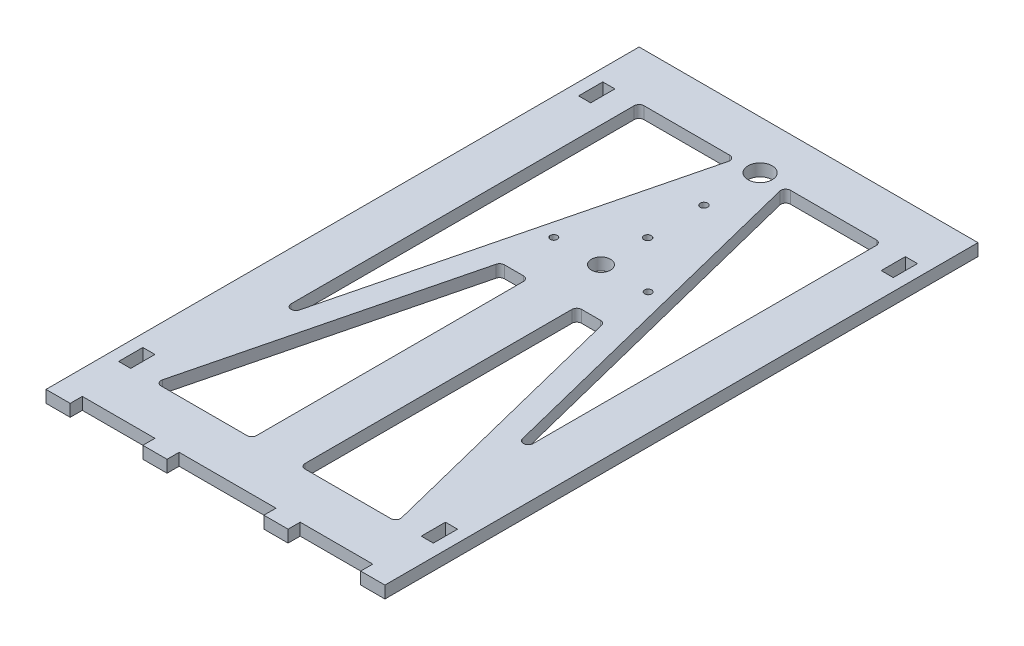
SolidWorks part; units mm, degrees
material "Beech"
ref_plane "Front Plane" through (0, 0, 0) normal (0, 0, 1) x (1, 0, 0)
ref_plane "Top Plane" through (0, 0, 0) normal (0, 1, 0) x (1, 0, 0)
ref_plane "Right Plane" through (0, 0, 0) normal (1, 0, 0) x (0, 0, -1)
sketch "Sketch1" plane through (0, 0, 0) normal (0, 1, 0) x (1, 0, 0)
  line L0 (0, 0) -> (177.8, 0)
  line L1 (0, 0) -> (0, 304.8)
  line L2 (177.8, 0) -> (177.8, 304.8)
  line L3 (0, 304.8) -> (177.8, 304.8)
  line L4 (0, 0) -> (12.7, 0)
  line L5 (0, 0) -> (0, -6.35)
  line L6 (12.7, 0) -> (12.7, -6.35)
  line L7 (0, -6.35) -> (12.7, -6.35)
  line L8 (177.8, 0) -> (165.1, 0)
  line L9 (177.8, 0) -> (177.8, -6.35)
  line L10 (165.1, 0) -> (165.1, -6.35)
  line L11 (177.8, -6.35) -> (165.1, -6.35)
  line L12 (127, 0) -> (114.3, 0)
  line L13 (127, 0) -> (127, -6.35)
  line L14 (114.3, 0) -> (114.3, -6.35)
  line L15 (127, -6.35) -> (114.3, -6.35)
  line L16 (50.8, 0) -> (63.5, 0)
  line L17 (50.8, 0) -> (50.8, -6.35)
  line L18 (63.5, 0) -> (63.5, -6.35)
  line L19 (50.8, -6.35) -> (63.5, -6.35)
  line L20 (165.1, 279.4) -> (171.45, 279.4)
  line L21 (165.1, 279.4) -> (165.1, 266.7)
  line L22 (171.45, 279.4) -> (171.45, 266.7)
  line L23 (165.1, 266.7) -> (171.45, 266.7)
  line L24 (6.35, 279.4) -> (12.7, 279.4)
  line L25 (6.35, 279.4) -> (6.35, 266.7)
  line L26 (12.7, 279.4) -> (12.7, 266.7)
  line L27 (6.35, 266.7) -> (12.7, 266.7)
  line L28 (6.35, 38.1) -> (12.7, 38.1)
  line L29 (6.35, 38.1) -> (6.35, 25.4)
  line L30 (12.7, 38.1) -> (12.7, 25.4)
  line L31 (6.35, 25.4) -> (12.7, 25.4)
  line L32 (165.1, 38.1) -> (171.45, 38.1)
  line L33 (165.1, 38.1) -> (165.1, 25.4)
  line L34 (171.45, 38.1) -> (171.45, 25.4)
  line L35 (165.1, 25.4) -> (171.45, 25.4)
  line L36 (76.2, 279.4) -> (25.4, 279.4)
  line L37 (25.4, 279.4) -> (25.4, 76.2)
  line L38 (25.4, 76.2) -> (76.2, 279.4)
  line L39 (101.6, 279.4) -> (152.4, 279.4)
  line L40 (152.4, 279.4) -> (152.4, 76.2)
  line L41 (152.4, 76.2) -> (101.6, 279.4)
  line L42 (25.4, 25.4) -> (61.675, 170.5)
  line L43 (61.675, 170.5) -> (76.2, 170.5)
  line L44 (76.2, 170.5) -> (76.2, 25.4)
  line L45 (76.2, 25.4) -> (25.4, 25.4)
  line L46 (101.6, 170.5) -> (116.125, 170.5)
  line L47 (116.125, 170.5) -> (152.4, 25.4)
  line L48 (152.4, 25.4) -> (101.6, 25.4)
  line L49 (101.6, 25.4) -> (101.6, 170.5)
  circle A0 centre (88.9, 279.4) radius 6.35
  circle A1 centre (88.9, 249.9) radius 1.935
  circle A2 centre (88.9, 220.4) radius 1.935
  circle A3 centre (88.9, 195.9) radius 5
  circle A4 centre (113.65, 195.9) radius 1.8542
  circle A5 centre (64.15, 195.9) radius 1.8542
  point P21 (88.9, 304.8)
  dimension "D8" = 12.7
  dimension "D14" = 3.87
  dimension "D15" = 3.87
  dimension "D18" = 10
  dimension "D19" = 3.7084
  dimension "D1" = 177.8
  dimension "D2" = 6.35
  dimension "D3" = 12.7
  dimension "D4" = 50.8
  dimension "D5" = 50.8
  dimension "D6" = 304.8
  dimension "D7" = 25.4
  dimension "D9" = 25.4
  dimension "D10" = 25.4
  dimension "D11" = 50.8
  dimension "D12" = 12.7
  dimension "D13" = 12.7
  dimension "D16" = 29.5
  dimension "D17" = 29.5
  dimension "D20" = 24.75
  dimension "D21" = 24.75
  dimension "D22" = 24.5
  dimension "D23" = 203.2
  dimension "D24" = 25.4
extrude "Front Panel" add sketch "Sketch1" along normal blind 6.35 contours L3 L1 L0 L2 A0 L35 L33 L32 L34 L31 L29 L28 L30 L27 L25 L24 L26 L23 L21 L20 L22 | L5 L7 L6 L0 | L17 L19 L18 L0 | L15 L13 L0 L14 | L11 L9 L0 L10 region at (88.9, 0, -152.6728) region at (6.35, 0, 3.175) region at (57.15, 0, 3.175) region at (171.45, 0, 3.175) region at (120.65, 0, 3.175)
fillet "Fillet1" radius 2.54 14 edges at (152.4, 3.175, -76.2) (152.4, 3.175, -279.4) (101.6, 3.175, -279.4) (76.2, 3.175, -279.4) (25.4, 3.175, -279.4) (25.4, 3.175, -76.2) (152.4, 3.175, -25.4) (101.6, 3.175, -25.4) (76.2, 3.175, -25.4) (25.4, 3.175, -25.4) (61.675, 3.175, -170.5) (76.2, 3.175, -170.5) (116.125, 3.175, -170.5) (101.6, 3.175, -170.5)
equation "\"CageLeftBottomEdge\"=22.11mm"
equation "\"CageLeftTopEdge\"=22.11mm"
equation "\"CageRightBottomEdge\"=21.63mm"
equation "\"CageRightTopEdge\"=21.63mm"
equation "\"CageHeight\"=86.04mm"
equation "\"CageLength\"=73.76mm"
equation "\"CageTopScrewClearance\"=10mm"
equation "\"CageBottomScrewClearance\"=25mm"
equation "\"CageLeftTopDepth\"= 11.65mm"
equation "\"CageLeftBottomDepth\"=11.11mm"
equation "\"CageLeftTopHeight\"=8.56175mm"
equation "\"CageLeftBottomHeight\"=16mm"
equation "\"CageRightTopDepth\"= 11.05mm"
equation "\"CageRightBottomDepth\"=10.58mm"
equation "\"CageRightTopHeight\"=9.6mm"
equation "\"CageRightBottomHeight\"=15.49mm"
equation "\"CageLeftTopChannelDepth\"=2.41908mm"
equation "\"CageLeftBottomChannelDepth\"=2.588mm"
equation "\"CageLeftChannelHeight\"=11.7mm"
equation "\"CageRightTopChannelDepth\"=2.32mm"
equation "\"CageRightBottomChannelDepth\"=2.318mm"
equation "\"CageRightChannelHeight\"=10mm"
equation "\"CageChanRelHeight\"=23.99mm"
equation "\"CageChanRelDepth\"=5.492mm"
equation "\"CageChamberRadius\"=16.261mm"
equation "\"CageScrewDiameter\"=4.8mm"
equation "\"CageSetScrewDiameter\"=3.5mm"
equation "\"CageAxleRadius\"=6.639mm"
equation "\"CageAxleKeyHeight\"=1.619mm"
equation "\"CageAxleKeyWidth\"=2.662mm"
equation "\"CageHoseWindowWidth\"=16.29mm"
equation "\"CageHoseWindowHeight\"=26.5mm"
equation "\"CageHoseWindow-Edge\"=8.89mm"
equation "\"CageScrew-VerticalEdge\"=5.0mm"
equation "\"CageScrew-HorizontalEdge\"=7.5mm"
equation "\"CageScrew-HoseCornerScrewEdge\"=4.45mm"
equation "\"CageAxle-BottomEdge\"=56.05mm"
equation "\"CageAxle-FrontEdge\"=46.03mm"
equation "\"CageBackSetScrew-Axle\"=40mm"
equation "\"CageFrontSetScrew-Axle\"=22mm"
equation "\"CageVelocityWindow-BackEdge\"=34.8mm"
equation "\"CageVelocityWindow-BottomEdge\"=27.55mm"
equation "\"CageVelocityWindowHeight\"=22.29mm"
equation "\"CageVelocityWindowWidth\"=12.61mm"
equation "\"TriggerSlot-BottomEdge\"=6.35mm"
equation "\"TriggerSlot-FrontEdge\"=15mm"
equation "\"TriggerSlotSize\"=6.7mm"
equation "\"TriggerRackOffset\"=.236224in"
equation "\"TriggerSlotSizeInt\"=.25in"
equation "\"MotorMountLegLength\"=.25in"
equation "\"GearOffset\"=.264907in"
equation "\"TriggerSlotSpacing\"=.25in"
equation "\"TriggerMiniSlotWidth\"=3.5mm"
equation "\"TriggerRackWidth\"=6.5mm"
equation "\"whitemotordepth\"=11.27mm"
equation "\"whitemotorbackdepth\"=3.845mm"
equation "\"whitemotoraxledepth\" = 3.5mm"
equation "\"whitemotoraxleoffset\"=11.4mm"
equation "\"whitemotorwidth\"=12.07mm"
equation "\"whitemotorheight\"=16.68mm"
equation "\"whitemotorcylinderlength\" =13.04mm"
equation "\"whitemotorcylinderradius\"=3.845mm"
equation "\"whitemotorcylinderoffset\"=2.35mm"
equation "\"whitemotorcutoutlength\"=1.88mm"
equation "\"whitemotorouterrad\"=5mm"
equation "\"whitemotorinnerrad\"=2.95mm"
equation "\"elasticracklength\"=2in"
equation "\"elasticrackpegsize\"=.25in"
equation "\"elasticrackpegbuffer\"=.125in"
equation "\"elasticrackpegspacing\"=1.76476378in"
equation "\"elasticbaybuffer\"=.25in"
equation "\"elasticdepth\"=.125in"
equation "\"elasticbaydepth\"=.75in"
equation "\"motormountwidth\"=12mm"
equation "\"motormountcornerfillet\"=3mm"
equation "\"pandiscradius\"=14in"
equation "\"towermaterialwidth\"=.25in"
equation "\"towerslotlength\"=.5in"
equation "\"towermarkerspace\"=5in"
equation "\"towerslothorizoffset\"=1in"
equation "\"towerslothorizspacing\"=2in"
equation "\"towerslotvertoffset\"=3in"
equation "\"towerslotvertspacing\"=1in"
equation "\"towerheight\"=12in"
equation "\"towerupslot\"=1in"
equation "\"D1@Sketch1\"=(\"towerslothorizoffset\"+\"towerslothorizspacing\"+\"towerslotlength\")*2"
equation "\"D2@Sketch1\"=\"towermaterialwidth\""
equation "\"D3@Sketch1\"=\"towerslotlength\""
equation "\"D4@Sketch1\"=\"towerslothorizspacing\""
equation "\"D5@Sketch1\"=\"towerslothorizspacing\""
equation "\"D6@Sketch1\"=\"towerheight\""
equation "\"D7@Sketch1\"=\"towerupslot\""
equation "\"toweraxle\"=.5in"
equation "\"D8@Sketch1\"=\"toweraxle\""
equation "\"D9@Sketch1\"=\"towerupslot\""
equation "\"D10@Sketch1\"= \"towerupslot\""
equation "\"D1@Front Panel\"=\"towermaterialwidth\""
equation "\"stepperouterrad\"=10mm"
equation "\"stepperscrewsize\"=3.45mm"
equation "\"stepperscrewc2c\"=49.5mm"
equation "\"stepperdepthoffset\"=24mm"
equation "\"stepperhorizoffset\"=22.91mm"
equation "\"shaftslotOD\"=18.8mm"
equation "\"shaftslotID\"=13.28mm"
equation "\"shaftkeywidth\"=2.67mm"
equation "\"shaftkeydepth\"=1.8mm"
equation "\"shaftcollartotaldepth\"=12.5mm"
equation "\"shaftsquaredepth\"=6mm"
equation "\"shaftsetscrewsize\"=3.5mm"
equation "\"shaftkeytightdepth\"=1.85mm"
equation "\"shaftslottightID\"=12.78mm"
equation "\"shaftsetscrewoffset\"=9mm"
equation "\"cagecollartotaldepth\"=10mm"
equation "\"cagecollartotalwidth\"=35mm"
equation "\"cagecollarbasedepth\"=4mm"
equation "\"ajaxaxlesize\"=3.87mm"
equation "\"D14@Sketch1\"=\"ajaxaxlesize\""
equation "\"D15@Sketch1\"=\"ajaxaxlesize\""
equation "\"ajax4020gap\"=29.5mm"
equation "\"D16@Sketch1\"=\"ajax4020gap\""
equation "\"D17@Sketch1\"=\"ajax4020gap\""
equation "\"D18@Sketch1\"=\"stepperouterrad\""
equation "\"D19@Sketch1\"=\"no6diam\""
equation "\"D20@Sketch1\"=\"stepperscrewc2c\"/2"
equation "\"D21@Sketch1\"=\"stepperscrewc2c\"/2"
equation "\"ajax4010gap\"=24.5mm"
equation "\"D22@Sketch1\"=\"ajax4010gap\""
equation "\"towerspeedwidth\"=2in"
equation "\"towerspeedheight\"=8in"
equation "\"towerspeedgap\"=2in"
equation "\"stepperaxleflat\"=.037in"
equation "\"stepperaxlerad\"=0.11811024in"
equation "\"ajaxinnercut\"=2.3mm"
equation "\"ajaxwidth\"=6.1mm"
equation "\"ajaxdiametral\"=25.8854"
equation "\"ajaxcutoutdepth\"=2.3mm"
equation "\"ajax20hubbuffer\"=6.1mm"
equation "\"ajax20hubholeoffset\"=.19685in"
equation "\"ajax20hubholesize\"=.059055in"
equation "\"ajax20cutoutint\"=13.4mm"
equation "\"ajax40hubholesize\"=7.21mm"
equation "\"ajax40hubholeoffset\"=10mm"
equation "\"ajax40hubbuffer\"=8.9mm"
equation "\"ajax40cutoutint\"=32.6mm"
equation "\"bearingpandiscrad\"=6.8in"
equation "\"bearingpandiscang\"=48.75deg"
equation "\"bearingclearholedist\"=4.7345in"
equation "\"bearingclearholesize\"=.5in"
equation "\"bearingclearholeang\"=22.5deg"
equation "\"bearingmountholedist\"=4.25in"
equation "\"bearingwirehole\"=1.5in"
equation "\"no6diam\"=.146in"
equation "\"D23@Sketch1\"=\"towerspeedheight\""
equation "\"D11@Sketch1\"=\"towerspeedwidth\""
equation "\"D24@Sketch1\"=2*\"toweraxle\""
equation "\"D12@Sketch1\"=\"toweraxle\""
equation "\"D13@Sketch1\"=\"toweraxle\""
equation "\"gearhubintdiam\"=30mm"
equation "\"gearhubintwid\"=15mm"
equation "\"shortconangle\"=20deg"
equation "\"shortconlen\"=.875in"
equation "\"longconlen\"=1.25in"
equation "\"longconangle\"=15deg"
